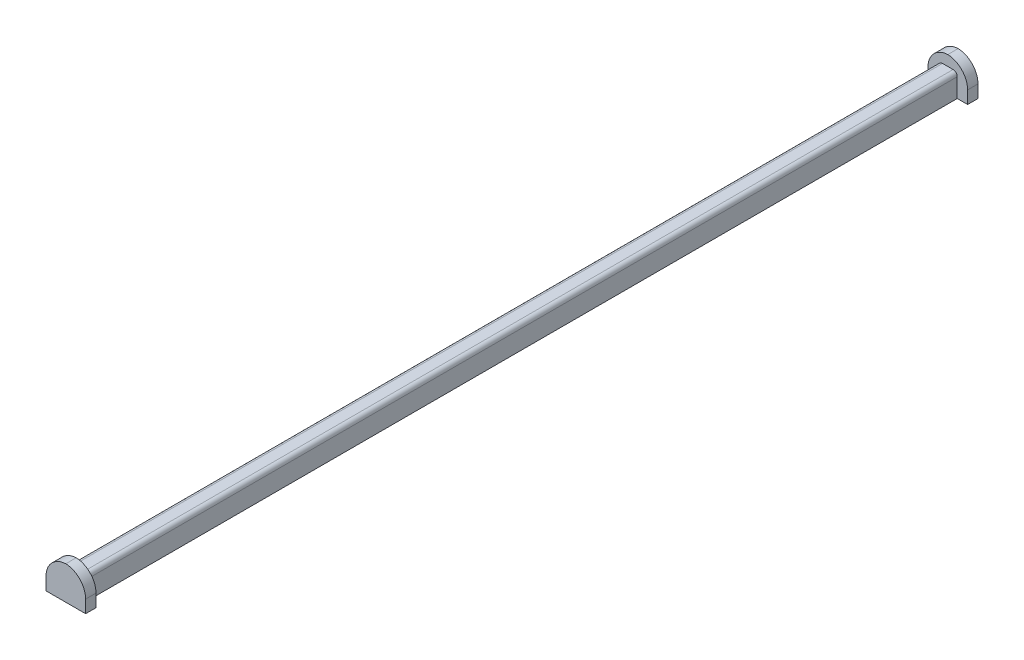
SolidWorks part; units mm, degrees
ref_plane "Front Plane" through (0, 0, 0) normal (0, 0, 1) x (1, 0, 0)
ref_plane "Top Plane" through (0, 0, 0) normal (0, 1, 0) x (1, 0, 0)
ref_plane "Right Plane" through (0, 0, 0) normal (1, 0, 0) x (0, 0, -1)
sketch "Sketch1" plane through (0, 0, 0) normal (0, 0, 1) x (1, 0, 0)
  line L0 (0, 0) -> (0, 1.905)
  line L3 (0, 3.81) -> (3.175, 3.81)
  line L6 (3.175, 1.905) -> (3.175, 0)
  line L7 (3.175, 0) -> (0, 0)
  line L16 (0, 3.81) -> (0, 1.905)
  line L17 (3.175, 3.81) -> (3.175, 1.905)
  line L18 (0.1429, 3.6671) -> (3.0321, 3.6671)
  line L19 (3.0321, 3.6671) -> (3.0321, 1.905)
  line L20 (3.0321, 1.905) -> (3.0321, 0.1429)
  line L21 (3.0321, 0.1429) -> (0.1429, 0.1429)
  line L22 (0.1429, 0.1429) -> (0.1429, 1.905)
  line L23 (0.1429, 3.6671) -> (0.1429, 1.905)
  dimension "D1" = 3.175
  dimension "D2" = 0.1429
  dimension "D3" = 1.905
extrude "Boss-Extrude1" add sketch "Sketch1" along normal blind 133.35 contours L22 L23 L18 L19 L20 L21
ref_plane "Plane1" through (1.5875, 0, 0) normal (1, 0, 0) x (0, 0, -1)
ref_plane "Plane2" through (0, 0, 66.675) normal (0, 0, 1) x (1, 0, 0)
sketch "Sketch2" plane through (0, 0, 133.35) normal (0, 0, 1) x (1, 0, 0)
  line L0 (0.1429, 0.1429) -> (0.1429, 3.6671) construction
  line L1 (-1.4446, 0.1429) -> (4.6196, 0.1429)
  line L2 (-1.4446, 0.1429) -> (-1.4446, 5.2546)
  line L3 (-1.4446, 5.2546) -> (4.6196, 5.2546)
  line L4 (4.6196, 0.1429) -> (4.6196, 5.2546)
  line L5 (3.0321, 3.6671) -> (3.0321, 0.1429) construction
  line L6 (0.1429, 3.6671) -> (3.0321, 3.6671) construction
  dimension "D1" = 1.5875
  dimension "D2" = 1.5875
  dimension "D3" = 1.5875
extrude "Boss-Extrude2" add sketch "Sketch2" along normal blind 1.5875 contours L2 L1 L4 L3
fillet "Fillet1" radius 3.175 2 edges at (-1.4446, 5.2546, 134.1438) (4.6196, 5.2546, 134.1438)
mirror "Mirror1" about plane through (0, 0, 66.675) normal (0, 0, 1) of "Fillet1", "Boss-Extrude2"
fillet "Fillet2" radius 0.635 2 edges at (0.1429, 3.6671, 66.675) (3.0321, 3.6671, 66.675)
